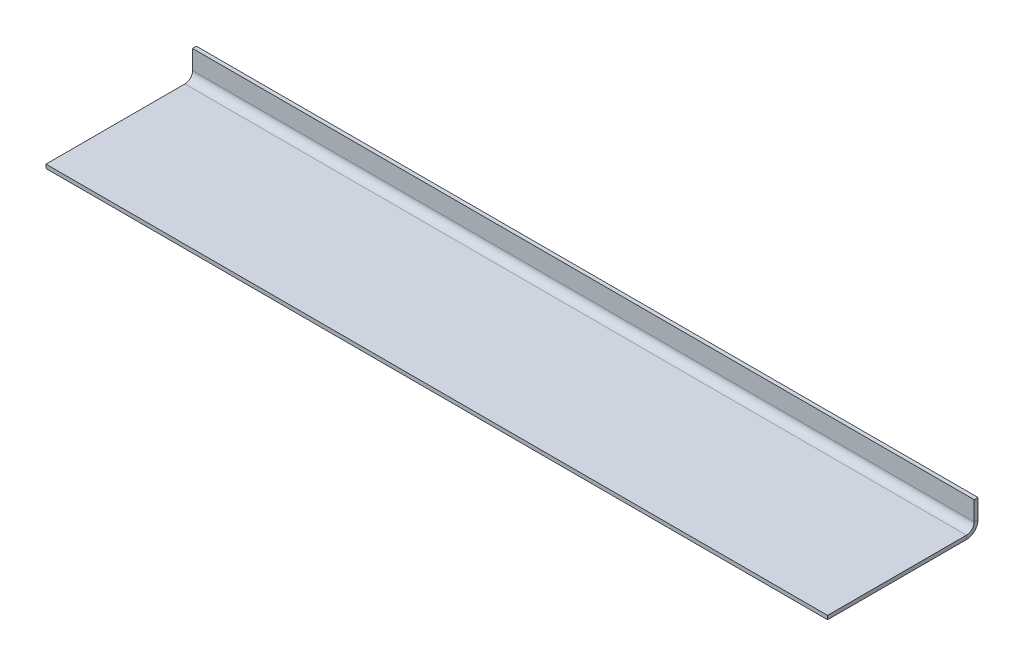
SolidWorks part; units mm, degrees
note: The reader was unsure of these and kept them because the rebuilt part matched: flange length of "Edge-Flange1".
material "6061-T6 (SS)"
ref_plane "X-Y Datum" through (0, 0, 0) normal (0, 0, 1) x (1, 0, 0)
ref_plane "X-Z Datum" through (0, 0, 0) normal (0, 1, 0) x (1, 0, 0)
ref_plane "Y-Z Datum" through (0, 0, 0) normal (1, 0, 0) x (0, 0, -1)
sketch "Sketch1" plane through (0, 0, 0) normal (0, 1, 0) x (1, 0, 0)
  line L1 (0, 0) -> (645.6578, 0)
  line L2 (0, 0) -> (0, 121.0767)
  line L3 (0, 121.0767) -> (645.6578, 121.0767)
  line L4 (645.6578, 0) -> (645.6578, 121.0767)
base flange "Base-Flange1" sketch "Sketch1" thickness 3.175 reverse thickness direction no parameters "D1"=9.525
edge flange "Edge-Flange1" sketch "Sketch8" flange angle 90 flange length 25.4 flange position material outside bend radius 6.35 thickness 3.175 relief rectangular parameters "D6"=10
sketch "Sketch8" plane through (0, 0, -121.0767) normal (0, 0, -1) x (-1, 0, 0)
  line L2 (-645.6578, 0) -> (-645.6578, 22.225)
  line L3 (-645.6578, 22.225) -> (0, 22.225)
  line L4 (0, 22.225) -> (0, 0)
  line L7 (-645.6578, 0) -> (0, 0) construction
  line L8 (-645.6578, 0) -> (0, 0)
bend "EdgeBend1" bend radius 6.35 bend angle 90 parameters "D5"=1
sketch "Bend-Lines1" [suppressed] plane through (0, 0, 0) normal (0, 1, 0) x (1, 0, 0)
sketch "Bounding-Box1" [suppressed] plane through (0, 0, 0) normal (0, 1, 0) x (1, 0, 0)
sheet metal parameters "Sheet-Metal1" thickness 3.175 parameters "D1"=9.525
flat pattern "Flat-Pattern1" [suppressed]
sketch "Bend-Lines2" plane through (0, 0, 0) normal (0, 1, 0) x (1, 0, 0)
sketch3d "Bounding-Box2" [suppressed]
  line L0 (-645.6578, 121.0767, 0) -> (0, 121.0767, 0) construction
  line L1 (-645.6578, 0, 0) -> (0, 0, 0) construction
  line L2 (-645.6578, 121.0767, 0) -> (-645.6578, 0, 0) construction
  line L3 (0, 121.0767, 0) -> (0, 0, 0) construction
sheet metal parameters "Sheet-Metal2" thickness 3.175 parameters "D1"=9.525
flat pattern "Flat-Pattern1"
sketch "Bend-Lines2" plane through (0, 0, 0) normal (0, 1, 0) x (1, 0, 0)
  line L0 (645.6578, 120.9608) -> (0, 120.9608) construction
  line L1 (645.6578, 120.9608) -> (0, 120.9608) construction
sketch3d "Bounding-Box2" [suppressed]
  line L0 (645.6578, 143.0699, 0) -> (0, 143.0699, 0) construction
  line L1 (645.6578, 0, 0) -> (0, 0, 0) construction
  line L2 (645.6578, 143.0699, 0) -> (645.6578, 0, 0) construction
  line L3 (0, 143.0699, 0) -> (0, 0, 0) construction
bend of the flat pattern "Flatten-<EdgeBend1>1"
